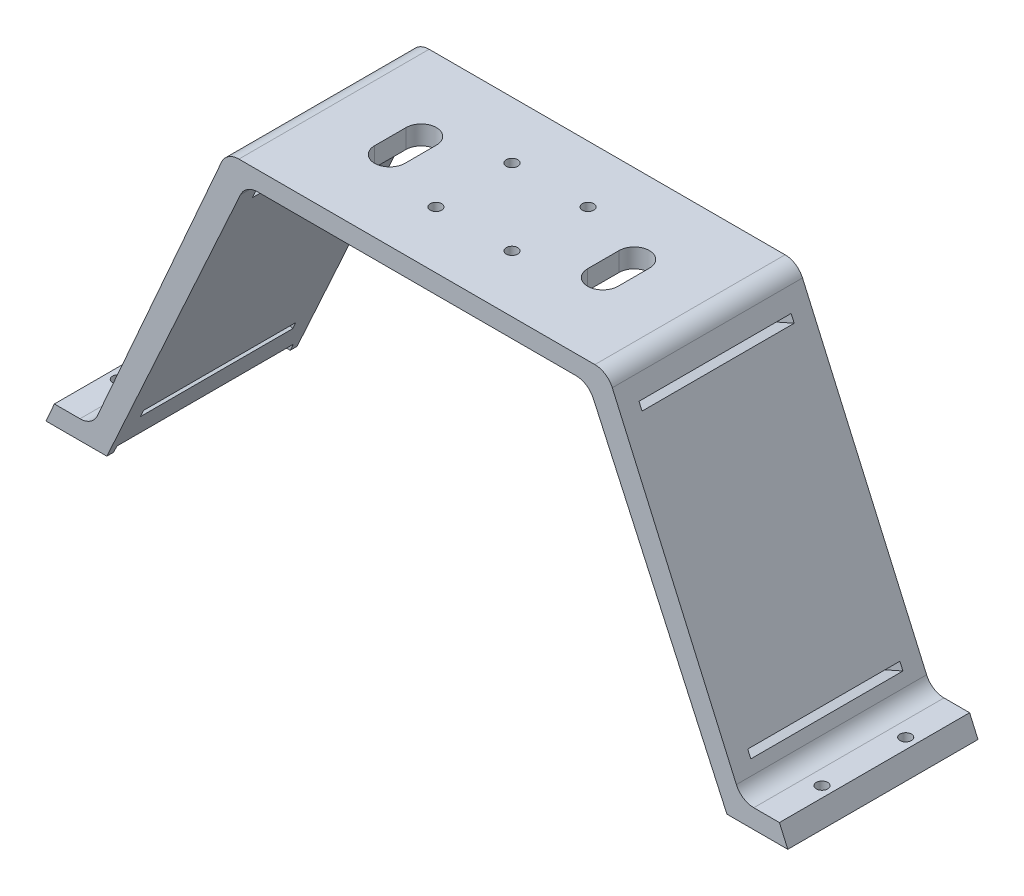
SolidWorks part; units mm, degrees
ref_plane "Front Plane" through (0, 0, 0) normal (0, 0, 1) x (1, 0, 0)
ref_plane "Top Plane" through (0, 0, 0) normal (0, 1, 0) x (1, 0, 0)
ref_plane "Right Plane" through (0, 0, 0) normal (1, 0, 0) x (0, 0, -1)
sketch "Sketch1" plane through (0, 0, 0) normal (0, 0, 1) x (1, 0, 0)
  line L0 (-87.5, 0) -> (87.5, 0)
  line L1 (-87.5, 0) -> (-50.05, 85)
  line L2 (-50.05, 85) -> (50.05, 85)
  line L3 (50.05, 85) -> (87.5, 0)
  point P4 (0, 0)
  dimension "D1" = 175
  dimension "D2" = 100.1
  dimension "D3" = 50.05
  dimension "D4" = 85
extrude "Boss-Extrude2" add sketch "Sketch1" along normal blind 50 contours L1 L2 L3 L0
sketch "Sketch3" plane through (0, 0, 50) normal (0, 0, 1) x (1, 0, 0)
  line L0 (-81.5, 0) -> (81.5, 0)
  line L1 (-87.5, 0) -> (87.5, 0) construction
  line L2 (81.5, 0) -> (45.05, 80)
  line L3 (45.05, 80) -> (-45.05, 80)
  line L4 (-45.05, 80) -> (-81.5, 0)
  line L5 (-50.05, 85) -> (50.05, 85) construction
  dimension "D1" = 163
  dimension "D2" = 6
  dimension "D3" = 90.1
  dimension "D4" = 45.05
  dimension "D5" = 5
extrude "Cut-Extrude1" cut sketch "Sketch3" against normal blind 50
fillet "Fillet1" radius 5 2 edges at (45.05, 80, 25) (-45.05, 80, 25)
sketch "Sketch5" plane through (73.2758, 32.2845, 0) normal (0.9151, 0.4032, 0) x (0, 0, -1)
  line L0 (0, 57.6053) -> (0, -35.2791) construction
  line L1 (-50, -35.2791) -> (0, -35.2791)
  line L2 (-50, -35.2791) -> (-50, -29.8151)
  line L3 (-50, -29.8151) -> (0, -29.8151)
  line L4 (0, -35.2791) -> (0, -29.8151)
  dimension "D1" = 5.464
sketch "Sketch8" plane through (0, 0, 0) normal (0, 1, 0) x (1, 0, 0)
  line L0 (93.2771, -25.8796) -> (149.3121, -25.8796)
sketch "Sketch9" plane through (0, 0, 0) normal (0, 1, 0) x (1, 0, 0)
  line L0 (-93.9767, -25.7952) -> (-133.9417, -25.7952)
sketch "Sketch10" plane through (-73.2758, 32.2845, 0) normal (-0.9151, 0.4032, 0) x (0, 0, 1)
  line L0 (0, -35.2791) -> (0, 57.6053) construction
  line L1 (50, -35.2791) -> (0, -35.2791)
  line L2 (50, -35.2791) -> (50, -29.8191)
  line L3 (50, -29.8191) -> (0, -29.8191)
  line L4 (0, -35.2791) -> (0, -29.8191)
  dimension "D1" = 5.46
extrude "Boss-Extrude4" add sketch "Sketch10" along direction (-1, 0, 0) on the side of the normal blind 10
extrude "Boss-Extrude5" add sketch "Sketch5" along direction (1, 0, 0) on the side of the normal blind 10 contours L3 L4 L1 L2
sketch "Sketch11" plane through (0, 4.9965, 0) normal (0, 1, 0) x (1, 0, 0)
  line L0 (-97.5, 0) -> (-97.5, -50) construction
  line L1 (-95.2986, -50) -> (-85.2986, -50) construction
  circle A0 centre (-92.5, -14) radius 1.5
  circle A1 centre (-92.5, -36) radius 1.5
  dimension "D1" = 22
  dimension "D2" = 5
  dimension "D3" = 14
extrude "Cut-Extrude2" cut sketch "Sketch11" against normal blind 10
sketch "Sketch12" plane through (0, 5.0002, 0) normal (0, 1, 0) x (1, 0, 0)
  line L0 (97.5, -50) -> (97.5, 0) construction
  line L1 (95.297, -50) -> (85.297, -50) construction
  circle A0 centre (92.5, -14) radius 1.5
  circle A1 centre (92.5, -36) radius 1.5
  dimension "D1" = 22
  dimension "D2" = 5
  dimension "D3" = 14
extrude "Cut-Extrude3" cut sketch "Sketch12" against normal blind 10
fillet "Fillet2" radius 5 2 edges at (85.297, 5.0002, 25) (-85.2986, 4.9965, 25)
fillet "Fillet3" radius 5 2 edges at (50.05, 85, 25) (-50.05, 85, 25)
sketch "Sketch13" plane through (0, 85, 0) normal (0, 1, 0) x (1, 0, 0)
  line L1 (-46.7892, 0) -> (-46.7892, -50) construction
  line L3 (-46.7892, 0) -> (46.7892, 0) construction
  line L4 (-46.7892, -50) -> (46.7892, -50) construction
  circle A0 centre (-9.9992, -15) radius 1.5
  circle A1 centre (10.0008, -15) radius 1.5
  circle A2 centre (-9.9992, -35) radius 1.5
  circle A3 centre (10.0008, -35) radius 1.5
  dimension "D1" = 20
  dimension "D2" = 20
  dimension "D3" = 20
  dimension "D4" = 20
  dimension "D5" = 36.79
  dimension "D6" = 15
extrude "Cut-Extrude5" cut sketch "Sketch13" against normal blind 10
sketch "Sketch14" plane through (0, 80, 0) normal (0, -1, 0) x (1, 0, 0)
  circle A0 centre (-9.9992, 35) radius 3
  circle A1 centre (-9.9992, 15) radius 3
  circle A2 centre (10.0008, 35) radius 3
  circle A3 centre (10.0008, 15) radius 3
extrude "Cut-Extrude6" cut sketch "Sketch14" against normal blind 2.5
sketch "Sketch15" plane through (0, 85, 0) normal (0, 1, 0) x (1, 0, 0)
  line L0 (-27.9992, -20.87) -> (-27.9992, -29.13) construction
  line L1 (-23.9992, -20.87) -> (-23.9992, -29.13)
  line L2 (-31.9992, -20.87) -> (-31.9992, -29.13)
  line L3 (28.0008, -20.87) -> (28.0008, -29.13) construction
  line L4 (32.0008, -20.87) -> (32.0008, -29.13)
  line L5 (24.0008, -20.87) -> (24.0008, -29.13)
  line L6 (-46.7892, 0) -> (46.7892, 0) construction
  line L7 (-46.7892, -50) -> (46.7892, -50) construction
  arc A0 (-23.9992, -20.87) -> (-31.9992, -20.87) centre (-27.9992, -20.87) ccw
  arc A1 (-31.9992, -29.13) -> (-23.9992, -29.13) centre (-27.9992, -29.13) ccw
  arc A2 (32.0008, -20.87) -> (24.0008, -20.87) centre (28.0008, -20.87) ccw
  arc A3 (24.0008, -29.13) -> (32.0008, -29.13) centre (28.0008, -29.13) ccw
  circle A4 centre (-9.9992, -15) radius 1.5 construction
  circle A5 centre (10.0008, -15) radius 1.5 construction
  point P2 (-27.9992, -25)
  point P7 (28.0008, -25)
  point P14 (28.0008, -16.87)
  dimension "D5" = 20.87
  dimension "D1" = 4
  dimension "D2" = 4
  dimension "D3" = 18
  dimension "D4" = 18
  dimension "D6" = 20.87
  dimension "D7" = 20.87
  dimension "D8" = 20.87
extrude "Cut-Extrude8" cut sketch "Sketch15" against normal blind 8.5
sketch "Sketch16" plane through (73.2758, 32.2845, 0) normal (0.9151, 0.4032, 0) x (0, 0, -1)
  line L2 (-45, 49.3444) -> (-5, 49.3444)
  line L3 (-45, 49.3444) -> (-45, 47.3444)
  line L4 (-45, 47.3444) -> (-5, 47.3444)
  line L5 (-5, 49.3444) -> (-5, 47.3444)
  line L6 (0, 54.3444) -> (0, -26.5542) construction
  line L7 (0, 54.3444) -> (-50, 54.3444) construction
  line L8 (-50, -26.5542) -> (0, -26.5542) construction
  line L9 (-45, -23.5542) -> (-5, -23.5542)
  line L10 (-45, -23.5542) -> (-45, -21.5542)
  line L11 (-45, -21.5542) -> (-5, -21.5542)
  line L12 (-5, -23.5542) -> (-5, -21.5542)
  line L13 (-50, 54.3444) -> (-50, -26.5542) construction
  point P14 (-45, -22.5542)
  dimension "D1" = 40
  dimension "D2" = 5
  dimension "D3" = 5
  dimension "D4" = 2
  dimension "D5" = 2
  dimension "D6" = 40
  dimension "D7" = 3
  dimension "D8" = 5
sketch "Sketch17" plane through (-73.2758, 32.2845, 0) normal (-0.9151, 0.4032, 0) x (0, 0, 1)
  line L2 (0, -26.5582) -> (0, 54.3444) construction
  line L3 (5, 49.3444) -> (45, 49.3444)
  line L4 (5, 49.3444) -> (5, 47.3444)
  line L5 (5, 47.3444) -> (45, 47.3444)
  line L6 (45, 49.3444) -> (45, 47.3444)
  line L7 (50, 54.3444) -> (0, 54.3444) construction
  line L8 (0, -26.5582) -> (50, -26.5582) construction
  line L9 (5, -23.5582) -> (45, -23.5582)
  line L10 (5, -23.5582) -> (5, -21.5582)
  line L11 (5, -21.5582) -> (45, -21.5582)
  line L12 (45, -23.5582) -> (45, -21.5582)
  dimension "D1" = 40
  dimension "D2" = 2
  dimension "D3" = 5
  dimension "D4" = 5
  dimension "D5" = 40
  dimension "D6" = 2
  dimension "D7" = 3
  dimension "D8" = 5
sketch "Sketch18" plane through (0, 0, 0) normal (0, -1, 0) x (1, 0, 0)
  line L0 (81.5, 0) -> (97.5, 0) construction
  line L1 (95.7, 1.8) -> (80.5, 1.8)
  line L2 (95.7, 1.8) -> (95.7, 48.2)
  line L3 (95.7, 48.2) -> (80.5, 48.2)
  line L4 (80.5, 1.8) -> (80.5, 48.2)
  line L5 (97.5, 50) -> (97.5, 0) construction
  line L6 (81.5, 50) -> (97.5, 50) construction
  dimension "D1" = 1.8
  dimension "D2" = 1.8
  dimension "D3" = 1.8
  dimension "D4" = 15.2
extrude "Cut-Extrude14" cut sketch "Sketch18" against normal blind 1.8 contours L1 L4 L3 L2
sketch "Sketch19" plane through (0, 0, 0) normal (0, -1, 0) x (1, 0, 0)
  line L0 (-97.5, 0) -> (-81.5, 0) construction
  line L1 (-95.7, 1.8) -> (-80.5, 1.8)
  line L2 (-95.7, 1.8) -> (-95.7, 48.2)
  line L3 (-95.7, 48.2) -> (-80.5, 48.2)
  line L4 (-80.5, 1.8) -> (-80.5, 48.2)
  line L5 (-97.5, 0) -> (-97.5, 50) construction
  line L6 (-97.5, 50) -> (-81.5, 50) construction
  dimension "D1" = 1.8
  dimension "D2" = 1.8
  dimension "D3" = 1.8
  dimension "D4" = 15.2
extrude "Cut-Extrude15" cut sketch "Sketch19" against normal blind 1.8
extrude "Cut-Extrude16" cut sketch "Sketch16" against normal blind 10
extrude "Cut-Extrude17" cut sketch "Sketch17" against normal blind 10
